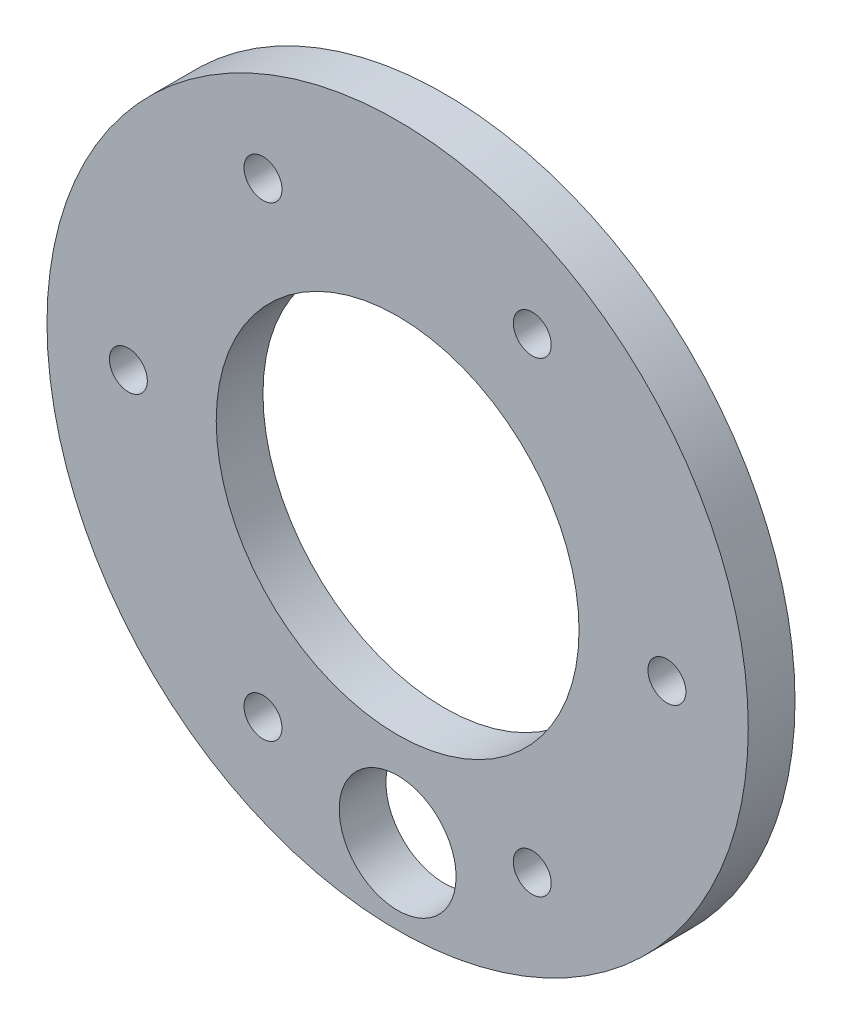
SolidWorks part; units mm, degrees
ref_plane "Front Plane" through (0, 0, 0) normal (0, 0, 1) x (1, 0, 0)
ref_plane "Top Plane" through (0, 0, 0) normal (0, 1, 0) x (1, 0, 0)
ref_plane "Right Plane" through (0, 0, 0) normal (1, 0, 0) x (0, 0, -1)
sketch "Sketch1" plane through (0, 0, 0) normal (0, 0, 1) x (1, 0, 0)
  circle A0 centre (95.25, 95.25) radius 95.25
extrude "F001_extrude_boss" add sketch "Sketch1" along normal blind 12.7
sketch "Sketch2" plane through (0, 0, 0) normal (0, 0, 1) x (1, 0, 0)
  circle A0 centre (95.25, 95.25) radius 49.276
extrude "F002_hole" cut sketch "Sketch2" along normal through all
sketch "Sketch3" plane through (0, 0, 0) normal (0, 0, 1) x (1, 0, 0)
  circle A0 centre (58.6751, 31.9004) radius 5.1562
extrude "F003_SeedHoleCut" cut sketch "Sketch3" along normal through all
ref_axis "PatternAxis1" through (95.25, 95.25, 12.7) along (0, 0, -1)
pattern_circular "F003_CircularPattern" count 6 over 360 about axis through (95.25, 95.25, 12.7) along (0, 0, -1) of "F003_SeedHoleCut"
sketch "Sketch4" plane through (0, 0, 0) normal (0, 0, 1) x (1, 0, 0)
  circle A0 centre (95.25, 20.574) radius 15.875
extrude "F004_extrude_cut" cut sketch "Sketch4" along normal through all
